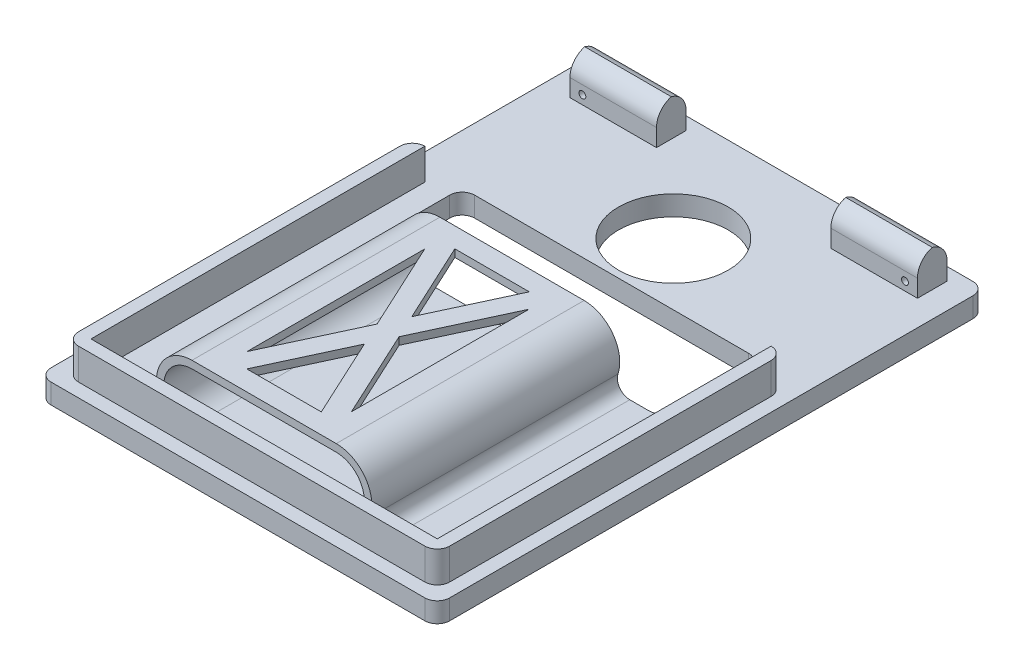
SolidWorks part; units mm, degrees
ref_plane "Front Plane" through (0, 0, 0) normal (0, 0, 1) x (1, 0, 0)
ref_plane "Top Plane" through (0, 0, 0) normal (0, 1, 0) x (1, 0, 0)
ref_plane "Right Plane" through (0, 0, 0) normal (1, 0, 0) x (0, 0, -1)
sketch "Sketch3" plane through (0, 0, 0) normal (0, 1, 0) x (1, 0, 0)
  line L0 (-75, 110) -> (75, 110)
  line L1 (-75, -105) -> (75, -105)
  line L2 (-75, -105) -> (-75, 105)
  line L4 (75, -105) -> (75, 105)
  line L5 (-75, -105) -> (75, 105) construction
  line L6 (-75, 105) -> (75, -105) construction
  line L7 (80, -105) -> (80, 105)
  line L8 (-75, -110) -> (75, -110)
  line L9 (-80, -105) -> (-80, 105)
  line L10 (-80, -110) -> (80, -110) construction
  line L11 (-80, -110) -> (-80, 110) construction
  line L12 (80, -110) -> (80, 110) construction
  line L13 (-80, 110) -> (80, 110) construction
  line L15 (-75, 105) -> (75, 105)
  line L19 (-75, 105) -> (75, 105) construction
  line L20 (-69.75, 104.9) -> (69.75, 104.9)
  line L21 (-69.75, 104.9) -> (-69.75, 93)
  line L22 (-69.75, 93) -> (69.75, 93)
  line L23 (69.75, 104.9) -> (69.75, 93)
  arc A0 (-75, -110) -> (-80, -105) centre (-75, -105) cw
  arc A1 (80, -105) -> (75, -110) centre (75, -105) cw
  arc A2 (75, 110) -> (80, 105) centre (75, 105) cw
  arc A3 (-75, 110) -> (-80, 105) centre (-75, 105) ccw
  point P0 (0, 0)
  point P5 (0, 93)
  dimension "D4" = 5
  dimension "D1" = 75
  dimension "D2" = 210
  dimension "D5" = 11.9
  dimension "D6" = 139.5
  dimension "D7" = 0.1
  dimension "D3" = 5
extrude "Boss-Extrude1" add sketch "Sketch3" along normal blind 8 contours L1 L4 L2 | L0 A3 L9 A0 L8 A1 L7 A2 L4 L1 L2 | L2 L4 | L23 L15 L21 L22 region at (0, 0, -107.2797) region at (0, 0, 5.5048) region at (0, 0, -98.95)
extrude "Boss-Extrude2" add sketch "Sketch3<7>" along normal blind 15 from surface contours L23 L15 L21 L22 region at (0, 0, -98.95) starting at face at (0, 8, 0)
sketch "Sketch3<7>" plane through (0, 0, 0) normal (0, 1, 0) x (1, 0, 0) same geometry as "Sketch3"
fillet "Fillet1" radius 8 2 edges at (0, 23, -93) (0, 23, -104.9)
sketch "Sketch4" plane through (0, 0, 0) normal (0, -1, 0) x (1, 0, 0)
  line L1 (-55, 0) -> (55, 0)
  line L2 (-60, -5) -> (-60, -35)
  line L3 (-55, -40) -> (55, -40)
  line L4 (60, -5) -> (60, -35)
  line L5 (-75, 110) -> (75, 110) construction
  line L6 (80, 105) -> (80, -105) construction
  line L7 (-75, -110) -> (75, -110) construction
  arc A0 (-55, 0) -> (-60, -5) centre (-55, -5) ccw
  arc A1 (-60, -35) -> (-55, -40) centre (-55, -35) ccw
  arc A2 (55, -40) -> (60, -35) centre (55, -35) ccw
  arc A3 (55, 0) -> (60, -5) centre (55, -5) cw
  point P4 (0, -40)
  dimension "D4" = 5
  dimension "D1" = 70
  dimension "D2" = 110
  dimension "D3" = 20
extrude "Cut-Extrude1" cut sketch "Sketch4" against normal up to next
sketch "Sketch5" plane through (0, 8, 0) normal (0, 1, 0) x (1, 0, 0)
  line L0 (75, -105) -> (75, 105) construction
  line L1 (-75, -105) -> (75, -105) construction
  line L2 (-75, -105) -> (-75, 105) construction
  line L3 (-75, 105) -> (75, 105) construction
  line L4 (75, 110) -> (-75, 110)
  line L5 (80, -105) -> (80, 105)
  line L6 (-75, -110) -> (75, -110)
  line L7 (-80, 105) -> (-80, -105)
  line L8 (75, 110) -> (-75, 110)
  line L9 (80, -105) -> (80, 105)
  line L10 (-75, -110) -> (75, -110)
  line L11 (-80, 105) -> (-80, -105)
  line L12 (69.75, 104.9) -> (-69.75, 104.9)
  line L13 (-69.75, 104.9) -> (-69.75, 93)
  line L14 (-69.75, 93) -> (69.75, 93)
  line L15 (69.75, 93) -> (69.75, 104.9)
  line L16 (69.75, 104.9) -> (-69.75, 104.9)
  line L17 (-69.75, 104.9) -> (-69.75, 93)
  line L18 (-69.75, 93) -> (69.75, 93)
  line L19 (69.75, 93) -> (69.75, 104.9)
  line L20 (75, -105) -> (75, 105)
  line L21 (-75, -105) -> (75, -105)
  line L22 (-75, -105) -> (-75, 105)
  line L23 (-75, 105) -> (75, 105)
  line L24 (-75, 35) -> (75, 35)
  line L25 (-69.5, 34.5) -> (-69.5, -99.5)
  line L26 (-69.5, -104.5) -> (69.5, -104.5)
  line L27 (-74.5, -99.5) -> (-74.5, 29.5)
  line L28 (-69.5, 34.5) -> (69.5, 34.5)
  line L29 (74.5, -99.5) -> (74.5, 29.5)
  line L30 (-69.5, -99.5) -> (69.5, -99.5)
  line L31 (69.5, -99.5) -> (69.5, 34.5)
  arc A0 (-74.5, 29.5) -> (-69.5, 34.5) centre (-69.5, 29.5) cw
  arc A1 (69.5, 34.5) -> (74.5, 29.5) centre (69.5, 29.5) cw
  arc A2 (69.5, -104.5) -> (74.5, -99.5) centre (69.5, -99.5) ccw
  arc A3 (-69.5, -104.5) -> (-74.5, -99.5) centre (-69.5, -99.5) cw
  arc A4 (80, 105) -> (75, 110) centre (75, 105) ccw
  arc A5 (75, -110) -> (80, -105) centre (75, -105) ccw
  arc A6 (-80, -105) -> (-75, -110) centre (-75, -105) ccw
  arc A7 (-75, 110) -> (-80, 105) centre (-75, 105) ccw
  arc A8 (80, 105) -> (75, 110) centre (75, 105) ccw
  arc A9 (75, -110) -> (80, -105) centre (75, -105) ccw
  arc A10 (-80, -105) -> (-75, -110) centre (-75, -105) ccw
  arc A11 (-75, 110) -> (-80, 105) centre (-75, 105) ccw
  point P26 (0, -104.5)
  point P42 (0, -99.5)
  dimension "D7" = 5
  dimension "D3" = 75
  dimension "D4" = 0.5
  dimension "D5" = 0.5
  dimension "D6" = 0.5
  dimension "D8" = 5
  dimension "D9" = 5
  dimension "D1" = 0
  dimension "D2" = 0
extrude "Boss-Extrude3" add sketch "Sketch5" along normal blind 12.5 contours A3 L26 A2 L29 A1 L31 L30 L25 A0 L27 region at (-71.5377, 8, 32.5)
sketch "Sketch6" plane through (0, 0, -104.9) normal (0, 0, -1) x (-1, 0, 0)
  line L0 (-69.75, 15) -> (-69.75, 8) construction
  line L1 (0, 0) -> (0, 22.7329) construction
  line L2 (-69.75, 22.7329) -> (69.75, 22.7329) construction
  circle A0 centre (-64.75, 11.5) radius 1.375
  circle A1 centre (64.75, 11.5) radius 1.375
  point P5 (-69.75, 11.5)
  dimension "D1" = 2.75
  dimension "D2" = 5
extrude "Cut-Extrude2" cut sketch "Sketch6" against normal up to next
sketch "Sketch8" plane through (0, 0, 99.5) normal (0, 0, -1) x (-1, 0, 0)
  line L0 (-28.95, 19.05) -> (28.95, 19.05) construction
  line L1 (-28.95, 30.1) -> (28.95, 30.1)
  line L2 (-28.95, 8) -> (28.95, 8)
  line L3 (69.5, 8) -> (-69.5, 8) construction
  line L4 (0, 19.05) -> (0, 0) construction
  line L5 (-28.95, 30.35) -> (28.95, 30.35)
  line L6 (-28.95, 7.75) -> (28.95, 7.75)
  line L7 (-28.95, 33.35) -> (28.95, 33.35)
  line L8 (-28.95, 4.75) -> (28.95, 4.75)
  line L9 (-38.0268, 8) -> (38.0268, 8)
  arc A0 (-28.95, 30.1) -> (-28.95, 8) centre (-28.95, 19.05) ccw
  arc A1 (28.95, 8) -> (28.95, 30.1) centre (28.95, 19.05) ccw
  arc A2 (28.95, 7.75) -> (28.95, 30.35) centre (28.95, 19.05) ccw
  arc A3 (-28.95, 30.35) -> (-28.95, 7.75) centre (-28.95, 19.05) ccw
  arc A4 (28.95, 4.75) -> (28.95, 33.35) centre (28.95, 19.05) ccw
  arc A5 (-28.95, 33.35) -> (-28.95, 4.75) centre (-28.95, 19.05) ccw
  point P2 (0, 19.05)
  line M6 (-69.5, 8) -> (69.5, 8)
  line M8 (69.5, 20.5) -> (-69.5, 20.5)
  dimension "D2" = 80
  dimension "D1" = 22.1
  dimension "D3" = 0.25
  dimension "D4" = 3
extrude "Boss-Extrude4" add sketch "Sketch8" along normal up to surface (99.5 mm away) contours L7 A5 A3 L5 A2 A4 M8 | L9 A4 A2 M8 | A5 A3 M8 M6 region at (41.6664, 21.373, 99.5) region at (39.6378, 13.5784, 99.5) region at (-39.6378, 13.5784, 99.5) up to face at (0, 4, 0)
fillet "Fillet2" radius 5 2 edges at (-38.0268, 8, 49.75) (38.0268, 8, 49.75)
sketch "Sketch9" plane through (0, 8, 0) normal (0, 1, 0) x (1, 0, 0)
  line L0 (69.75, 98.95) -> (-69.75, 98.95) construction
  line L1 (-35, 104.9) -> (35, 104.9)
  line L2 (-35, 104.9) -> (-35, 93)
  line L3 (-35, 93) -> (35, 93)
  line L4 (35, 104.9) -> (35, 93)
  line L5 (-35, 104.9) -> (35, 93) construction
  line L6 (-35, 93) -> (35, 104.9) construction
  line L7 (69.75, 93) -> (-69.75, 93) construction
  point P0 (0, 98.95)
  dimension "D1" = 70
extrude "Cut-Extrude3" cut sketch "Sketch9" along normal up to next
sketch "Sketch10" plane through (0, 33.35, 0) normal (0, 1, 0) x (1, 0, 0)
  line L0 (-20.95, -85.4223) -> (-4.4091, -49.75)
  line L1 (-4.4091, -49.75) -> (-20.95, -14.0777)
  line L2 (-14.95, -8) -> (0, -40.2413)
  line L3 (0, -40.2413) -> (14.95, -8)
  line L4 (28.95, 0) -> (-28.95, 0)
  line L5 (-28.95, 0) -> (-28.95, -99.5)
  line L6 (-28.95, -99.5) -> (28.95, -99.5)
  line L7 (28.95, -99.5) -> (28.95, 0)
  line L8 (28.95, 0) -> (-28.95, 0)
  line L9 (-28.95, 0) -> (-28.95, -99.5)
  line L10 (-28.95, -99.5) -> (28.95, -99.5)
  line L11 (28.95, -99.5) -> (28.95, 0)
  line L12 (0, -8) -> (0, -91.5) construction
  line L13 (20.95, -49.75) -> (-20.95, -49.75) construction
  line L14 (20.95, -85.4223) -> (4.4091, -49.75)
  line L15 (4.4091, -49.75) -> (20.95, -14.0777)
  line L16 (20.95, -8) -> (-20.95, -8)
  line L17 (-20.95, -8) -> (-20.95, -91.5)
  line L18 (-20.95, -91.5) -> (20.95, -91.5)
  line L19 (20.95, -91.5) -> (20.95, -8)
  line L20 (20.95, -8) -> (-20.95, -8)
  line L21 (-20.95, -8) -> (-20.95, -91.5)
  line L22 (-20.95, -91.5) -> (20.95, -91.5)
  line L23 (20.95, -91.5) -> (20.95, -8)
  line L24 (0, -59.2587) -> (14.95, -91.5)
  line L25 (-14.95, -91.5) -> (0, -59.2587)
  dimension "D3" = 8
  dimension "D4" = 6
  dimension "D1" = 0
  dimension "D2" = 8
extrude "Cut-Extrude4" cut sketch "Sketch10" against normal up to next contours L14 L23 L15 | L25 L22 L24 | L3 L20 L2 | L1 L21 L0 region at (-15.4364, 33.35, 49.75) region at (0, 33.35, 80.7529) region at (0, 33.35, 18.7471) region at (15.4364, 33.35, 49.75)
sketch "Sketch11" plane through (0, 0, 0) normal (0, -1, 0) x (1, 0, 0)
  circle A0 centre (0, -64.78) radius 22
  dimension "D1" = 44
extrude "Cut-Extrude5" cut sketch "Sketch11" against normal up to next
